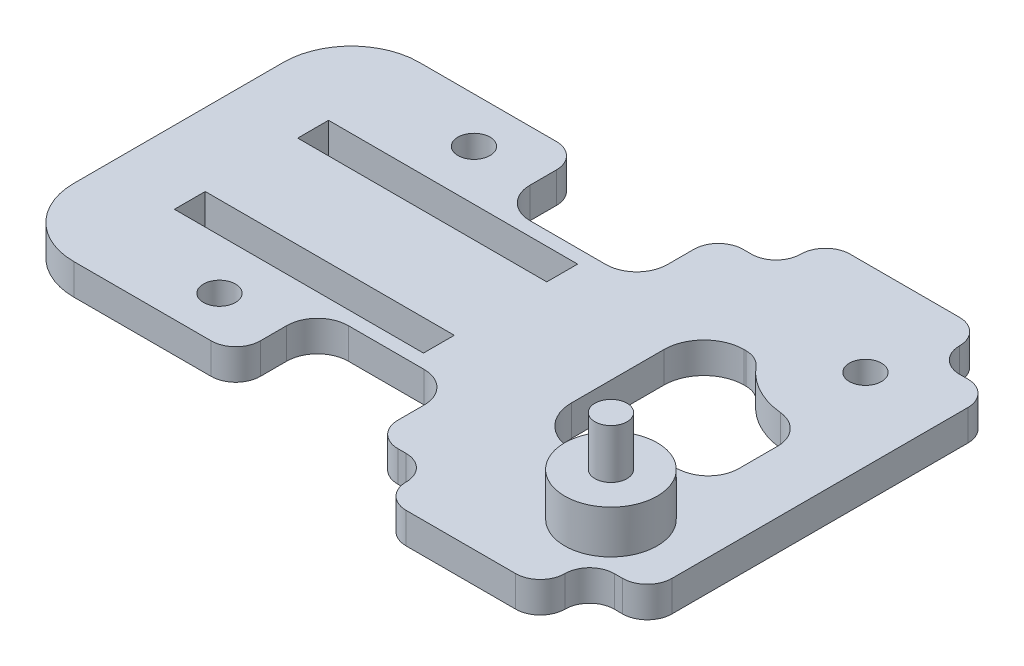
SolidWorks part; units mm, degrees
other "下垫片"
ref_plane "前视基准面" through (0, 0, 0) normal (0, 0, 1) x (1, 0, 0)
ref_plane "上视基准面" through (0, 0, 0) normal (0, 1, 0) x (1, 0, 0)
ref_plane "右视基准面" through (0, 0, 0) normal (1, 0, 0) x (0, 0, -1)
other "Configuration Table"
sketch "草图1" plane through (0, 0, 0) normal (0, 1, 0) x (1, 0, 0)
  line L0 (-89.3251, 0) -> (102.0425, 0) construction
  line L1 (0, 56.7239) -> (0, -62.578) construction
  line L2 (-47.2, -7.5) -> (-6.8, -7.5)
  line L3 (-47.2, 12.5) -> (-6.8, 12.5)
  line L4 (-47.2, 12.5) -> (-47.2, 7.5)
  line L5 (-47.2, 7.5) -> (-6.8, 7.5)
  line L6 (-6.8, 12.5) -> (-6.8, 7.5)
  line L7 (-47.2, 12.5) -> (-6.8, 7.5) construction
  line L8 (-47.2, 7.5) -> (-6.8, 12.5) construction
  line L9 (-6.8, -12.5) -> (-6.8, -7.5)
  line L10 (-47.2, -12.5) -> (-6.8, -12.5)
  line L11 (-47.2, -12.5) -> (-47.2, -7.5)
  line L14 (-21.75, -26.5375) -> (-21.75, -14.7375)
  line L15 (-21.75, -14.7375) -> (0.55, -14.7375)
  line L16 (0.55, -26.5375) -> (0.55, -14.7375)
  line L17 (-21.75, -26.5375) -> (0.55, -14.7375) construction
  line L18 (-21.75, -14.7375) -> (0.55, -26.5375) construction
  line L19 (-21.75, 14.7375) -> (0.55, 14.7375)
  line L20 (0.55, 26.5375) -> (0.55, 14.7375)
  line L22 (-21.75, 26.5375) -> (-21.75, 14.7375)
  line L23 (-21.75, 30.0095) -> (0.55, 30.0095)
  line L25 (-21.75, -26.5375) -> (-21.75, -30.0095)
  line L26 (-21.75, -30.0095) -> (0.55, -30.0095)
  line L27 (0.55, -26.5375) -> (0.55, -30.0095)
  line L28 (0.55, 26.5375) -> (0.55, 30.0095)
  line L30 (-21.75, 26.5375) -> (-21.75, 30.0095)
  circle A0 centre (-31.75, 20.6375) radius 2.6
  circle A4 centre (31.75, 20.6375) radius 2.6
  circle A5 centre (31.75, -20.6375) radius 2.6
  circle A6 centre (-31.75, -20.6375) radius 2.6
  point P13 (-27, 10)
  point P22 (-10.6, -20.6375)
  point P35 (-27, 10)
  dimension "D5" = 5.2
  dimension "D11" = 5.2
  dimension "D1" = 40.4
  dimension "D2" = 31.75
  dimension "D3" = 5
  dimension "D4" = 20.6375
  dimension "D6" = 10
  dimension "D7" = 22.3
  dimension "D8" = 11.8
  dimension "D9" = 0
  dimension "D10" = 31.2
  dimension "D12" = 5
  dimension "D13" = 40.4
  dimension "D14" = 27
  dimension "D15" = 10
  dimension "D16" = 2.2375
sketch "草图3" plane through (0, 0, 0) normal (0, 1, 0) x (1, 0, 0)
  line L0 (-40, 28) -> (-59, 28)
  line L1 (-40, -28) -> (9.9, -28)
  line L3 (-40, 28) -> (9.9, 28)
  line L5 (-40, -28) -> (40, 28) construction
  line L6 (-40, 28) -> (40, -28) construction
  line L7 (-59, 28) -> (-59, -28)
  line L8 (-59, -28) -> (-40, -28)
  line L10 (45, 28) -> (45, -28)
  line L15 (-45.7746, 0) -> (58.2399, 0) construction
  line L19 (9.9, 28) -> (9.9, 36)
  line L20 (9.9, 36) -> (35.65, 36)
  line L21 (35.65, 36) -> (35.65, 28)
  line L22 (35.65, 28) -> (45, 28)
  line L23 (35.65, -28) -> (45, -28)
  line L24 (35.65, -36) -> (35.65, -28)
  line L25 (9.9, -36) -> (35.65, -36)
  line L26 (9.9, -28) -> (9.9, -36)
  point P0 (0, 0)
  dimension "D1" = 56
  dimension "D2" = 80
  dimension "D3" = 19
  dimension "D4" = 5
  dimension "D5" = 9.35
  dimension "D6" = 8
  dimension "D7" = 25.75
extrude "凸台-拉伸1" add sketch "草图3" along normal blind 5
extrude "切除-拉伸1" cut sketch "草图1" along normal up to surface (5 mm away) up to face at (12.85, 5, 0)
sketch "草图5" plane through (0, 5, 0) normal (0, 1, 0) x (1, 0, 0)
  circle A0 centre (31.75, -20.6375) radius 7.5
  dimension "D1" = 15
extrude "凸台-拉伸2" add sketch "草图5" along normal blind 7
sketch "草图6" plane through (0, 12, 0) normal (0, 1, 0) x (1, 0, 0)
  circle A0 centre (31.75, -20.6375) radius 2.6
  dimension "D1" = 5.2
extrude "凸台-拉伸3" add sketch "草图6" along normal blind 8
fillet "圆角1" radius 5 4 edges at (0.55, 2.5, 14.7375) (-21.75, 2.5, 14.7375) (0.55, 2.5, -14.7375) (-21.75, 2.5, -14.7375)
fillet "圆角2" radius 4 14 edges at (0.55, 2.5, 28) (-21.75, 2.5, 28) (0.55, 2.5, -28) (-21.75, 2.5, -28) (9.9, 2.5, 28) (9.9, 2.5, 36) (35.65, 2.5, 36) (35.65, 2.5, 28) (45, 2.5, 28) (45, 2.5, -28) (35.65, 2.5, -28) (35.65, 2.5, -36) (9.9, 2.5, -36) (9.9, 2.5, -28)
sketch "草图7" plane through (0, 0, 0) normal (0, -1, 0) x (1, 0, 0)
  line L0 (-31.75, 20.6375) -> (31.75, 20.6375) construction
  line L1 (0, 27.9483) -> (0, -23.2551) construction
sketch "草图14" plane through (0, 5, 0) normal (0, 1, 0) x (1, 0, 0)
  line L0 (-11.6114, 0) -> (10.899, 0) construction
  line L1 (21.04, 14) -> (12.2, 14)
  line L2 (12.2, 14) -> (12.2, -14)
  line L3 (45, -24) -> (45, 24) construction
  line L4 (35, 8.4639) -> (35, -8.4639)
  line L5 (21.04, -14) -> (12.2, -14)
  arc A0 (35, 8.4639) -> (21.04, 14) centre (31.75, 20.6375) cw
  arc A1 (35, -8.4639) -> (21.04, -14) centre (31.75, -20.6375) ccw
  point P5 (35, 0)
  point P7 (21.04, 14)
  point P8 (35, 8.4639)
  point P18 (12.2, 0)
  dimension "D1" = 12.6
  dimension "D2" = 14
  dimension "D3" = 12.2
  dimension "D4" = 10
extrude "切除-拉伸6" cut sketch "草图14" against normal through all
fillet "圆角5" radius 4 2 edges at (21.04, 2.5, 14) (21.04, 2.5, -14)
fillet "圆角6" radius 11 2 edges at (-59, 2.5, 28) (-59, 2.5, -28)
fillet "圆角7" radius 6.5 2 edges at (12.2, 2.5, 14) (12.2, 2.5, -14)
fillet "圆角8" radius 5 2 edges at (35, 2.5, 8.4639) (35, 2.5, -8.4639)
